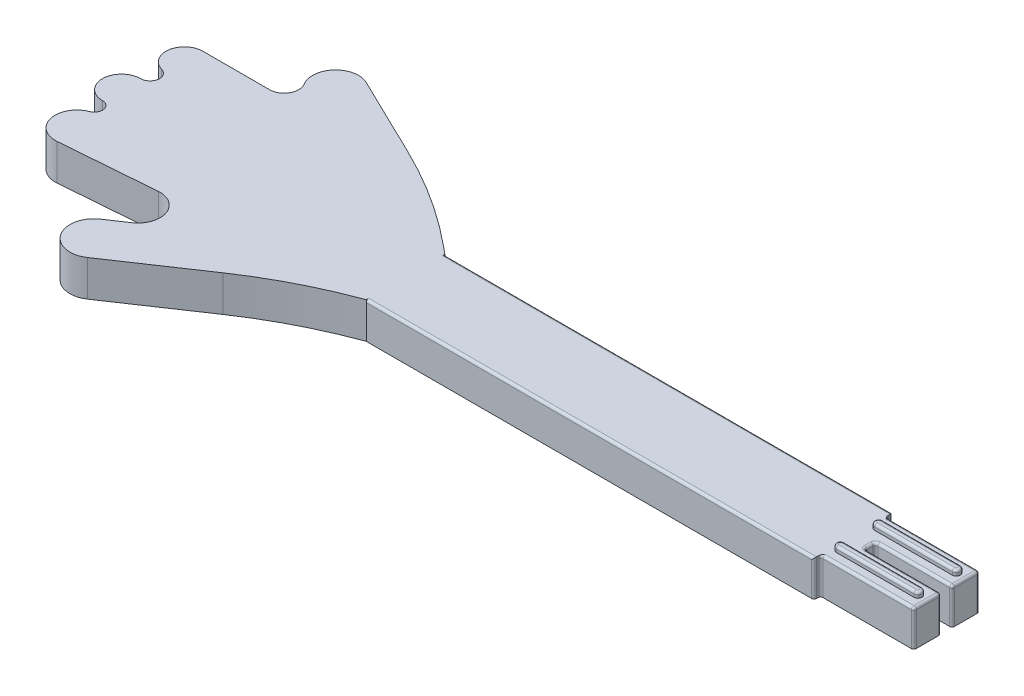
SolidWorks part; units mm, degrees
ref_plane "Front Plane" through (0, 0, 0) normal (0, 0, 1) x (1, 0, 0)
ref_plane "Top Plane" through (0, 0, 0) normal (0, 1, 0) x (1, 0, 0)
ref_plane "Right Plane" through (0, 0, 0) normal (1, 0, 0) x (0, 0, -1)
sketch "Sketch1" plane through (0, 0, 0) normal (0, 1, 0) x (1, 0, 0)
  line L0 (0, 0) -> (18.25, 0)
  line L1 (18.75, 0.5) -> (18.75, 5)
  line L2 (18.25, 5.5) -> (3.85, 5.5)
  line L3 (3.35, 6) -> (3.35, 7.2)
  line L4 (3.85, 7.7) -> (18.25, 7.7)
  line L5 (18.75, 8.2) -> (18.75, 12.7)
  line L6 (18.25, 13.2) -> (0, 13.2)
  line L7 (0, 13.2) -> (0, 0)
  arc A0 (18.75, 12.7) -> (18.25, 13.2) centre (18.25, 12.7) ccw
  arc A1 (18.25, 7.7) -> (18.75, 8.2) centre (18.25, 8.2) ccw
  arc A2 (3.35, 7.2) -> (3.85, 7.7) centre (3.85, 7.2) cw
  arc A3 (3.85, 5.5) -> (3.35, 6) centre (3.85, 6) cw
  arc A4 (18.75, 5) -> (18.25, 5.5) centre (18.25, 5) ccw
  arc A5 (18.25, 0) -> (18.75, 0.5) centre (18.25, 0.5) ccw
  point P15 (3.35, 7.7)
  point P18 (3.35, 5.5)
  point P21 (18.75, 5.5)
  point P24 (18.75, 0)
  point P25 (3.35, 6.6)
  point P26 (0, 6.6)
  dimension "D5" = 0.5
  dimension "D1" = 18.75
  dimension "D2" = 13.2
  dimension "D3" = 15.4
  dimension "D4" = 5.5
extrude "Boss-Extrude1" add sketch "Sketch1" along normal blind 7.25
sketch "Sketch2" plane through (0, 7.25, 0) normal (0, 1, 0) x (1, 0, 0)
  line L0 (1.25, 2.75) -> (16.85, 2.75) construction
  line L1 (1.25, 3.55) -> (16.85, 3.55)
  line L2 (1.25, 1.95) -> (16.85, 1.95)
  line L3 (0, 6.6) -> (21.8378, 6.6) construction
  line L4 (0, 13.2) -> (0, 0) construction
  line L5 (18.75, 0.5) -> (18.75, 5) construction
  line L6 (1.25, 10.45) -> (16.85, 10.45) construction
  line L7 (1.25, 9.65) -> (16.85, 9.65)
  line L8 (1.25, 11.25) -> (16.85, 11.25)
  arc A0 (1.25, 3.55) -> (1.25, 1.95) centre (1.25, 2.75) ccw
  arc A1 (16.85, 1.95) -> (16.85, 3.55) centre (16.85, 2.75) ccw
  arc A2 (1.25, 9.65) -> (1.25, 11.25) centre (1.25, 10.45) cw
  arc A3 (16.85, 11.25) -> (16.85, 9.65) centre (16.85, 10.45) cw
  point P2 (9.05, 2.75)
  point P13 (18.75, 2.75)
  point P16 (17.65, 2.75)
  point P19 (9.05, 10.45)
  dimension "D1" = 15.6
  dimension "D2" = 1.6
  dimension "D3" = 1.1
extrude "Boss-Extrude2" add sketch "Sketch2" along normal blind 1.1
fillet "Fillet1" radius 0.5 21 edges at (17.65, 8.35, -2.75) (0.45, 8.35, -2.75) (0.45, 8.35, -10.45) (17.65, 8.35, -10.45) (9.05, 8.35, -11.25) (9.05, 8.35, -9.65) (9.05, 8.35, -3.55) (9.05, 8.35, -1.95) (18.6036, 7.25, -13.0536) (18.75, 7.25, -10.45) (18.6036, 7.25, -7.8464) (3.35, 7.25, -6.6) (3.4964, 7.25, -7.5536) (3.4964, 7.25, -5.6464) (18.6036, 7.25, -0.1464) (18.6036, 7.25, -5.3536) (18.75, 7.25, -2.75) (9.125, 7.25, 0) (11.05, 7.25, -5.5) (11.05, 7.25, -7.7) (9.125, 7.25, -13.2)
sketch "Sketch4" plane through (0, 0, 0) normal (0, 1, 0) x (1, 0, 0)
  line L0 (0, -1.3) -> (0, 14.5)
  line L1 (0, 12.7) -> (0, 0.5) construction
  line L2 (0, 14.5) -> (-90, 14.5)
  line L3 (-90, 14.5) -> (-90, -1.3)
  line L4 (-90, -1.3) -> (0, -1.3)
  point P4 (0, 6.6)
  dimension "D1" = 15.8
  dimension "D2" = 90
extrude "Boss-Extrude3" add sketch "Sketch4" along normal up to surface (7.25 mm away) up to face at (8.5986, 7.25, -6.6)
fillet "Fillet3" radius 0.5 8 edges at (0, 7.1036, -13.0536) (0, 7.1036, -0.1464) (-45, 7.25, -14.5) (0, 3.625, -14.5) (0, 3.375, -13.2) (0, 3.375, 0) (0, 3.625, 1.3) (-45, 7.25, 1.3)
sketch "Sketch5" plane through (0, 7.25, 0) normal (0, 1, 0) x (1, 0, 0)
  line L0 (-90, 14.5) -> (-91.6946, 15.8939)
  line L1 (-111.5706, 28.6346) -> (-127.8092, 36.513)
  line L2 (-136.2765, 25.5384) -> (-149.667, 25.5384)
  line L3 (-148.6777, -4.8212) -> (-129.7666, -3.3356)
  line L4 (-126.9449, -11.4333) -> (-130.7433, -13.9887)
  line L5 (-125.3724, -21.9723) -> (-109.0931, -11.0206)
  line L6 (-90, 14.5) -> (-90, -1.3)
  arc A0 (-127.8092, 36.513) -> (-133.7704, 29.9793) centre (-129.8224, 32.3635) ccw
  arc A1 (-133.7704, 29.9793) -> (-136.2765, 25.5384) centre (-136.2765, 28.466) cw
  arc A2 (-149.667, 25.5384) -> (-150.6584, 18.2467) centre (-149.667, 21.8252) ccw
  arc A3 (-150.6584, 18.2467) -> (-151.1678, 14.5) centre (-151.1678, 16.408) cw
  arc A4 (-151.1678, 14.5) -> (-151.1678, 6.8463) centre (-151.1678, 10.6731) ccw
  arc A5 (-151.1678, 6.8463) -> (-150.5778, 3.6363) centre (-151.1678, 5.187) cw
  arc A6 (-150.5778, 3.6363) -> (-148.6777, -4.8212) centre (-149.0207, -0.4561) ccw
  arc A7 (-129.7666, -3.3356) -> (-126.9449, -11.4333) centre (-129.4195, -7.7551) cw
  arc A8 (-130.7433, -13.9887) -> (-125.3724, -21.9723) centre (-128.0579, -17.9805) ccw
  arc A9 (-109.0931, -11.0206) -> (-90, -1.3) centre (-59.6694, -84.487) cw
  arc A10 (-91.6946, 15.8939) -> (-111.5706, 28.6346) centre (-155.221, -61.3356) ccw
  dimension "D1" = 100
  dimension "D2" = 16.2386
  dimension "D5" = 88.5439
  dimension "D8" = 3.7132
  dimension "D9" = 3.8269
  dimension "D10" = 4.3786
  dimension "D12" = 4.4331
  dimension "D13" = 4.8111
  dimension "D18" = 1.6592
  dimension "D19" = 1.908
  dimension "D20" = 2.9276
  dimension "D3" = 19.0931
  dimension "D4" = 19.6203
  dimension "D6" = 1.6946
  dimension "D7" = 13.3905
  dimension "D11" = 18.9111
  dimension "D14" = 4.5779
  dimension "D15" = 2.1942
  dimension "D16" = 16.2793
  dimension "D17" = 18.9694
  dimension "D21" = 18.0488
  dimension "D22" = 46.2765
  dimension "D23" = 43.7704
  dimension "D24" = 60.5778
  dimension "D25" = 36.9449
extrude "Boss-Extrude4" add sketch "Sketch5" against normal up to surface (7.25 mm away) up to face at (-0.7906, 0, -6.6)
